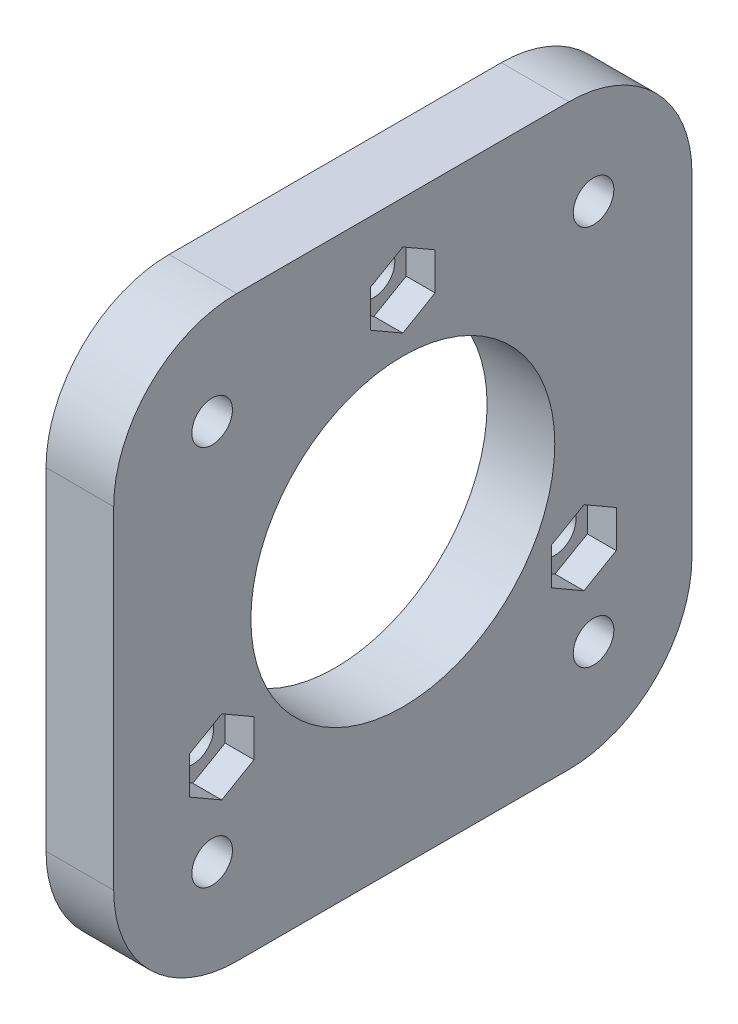
SolidWorks part; units mm, degrees
ref_plane "Alzado" through (0, 0, 0) normal (0, 0, 1) x (1, 0, 0)
ref_plane "Planta" through (0, 0, 0) normal (0, 1, 0) x (1, 0, 0)
ref_plane "Vista lateral" through (0, 0, 0) normal (1, 0, 0) x (0, 0, -1)
sketch "Croquis1" plane through (0, 0, 0) normal (1, 0, 0) x (0, 0, -1)
  line L0 (23.5, -23.5) -> (23.5, 23.5)
  line L1 (-15.5, -15.5) -> (15.5, -15.5) construction
  line L2 (-15.5, -15.5) -> (-15.5, 15.5) construction
  line L3 (-15.5, 15.5) -> (15.5, 15.5) construction
  line L4 (15.5, -15.5) -> (15.5, 15.5) construction
  line L5 (-15.5, -15.5) -> (15.5, 15.5) construction
  line L6 (-15.5, 15.5) -> (15.5, -15.5) construction
  line L7 (-23.5, 23.5) -> (23.5, 23.5)
  line L8 (-23.5, -23.5) -> (-23.5, 23.5)
  line L9 (-23.5, -23.5) -> (23.5, -23.5)
  circle A0 centre (-15.5, 15.5) radius 1.65
  circle A1 centre (15.5, 15.5) radius 1.65
  circle A2 centre (15.5, -15.5) radius 1.65
  circle A3 centre (-15.5, -15.5) radius 1.65
  point P0 (0, 0)
  point P16 (0, 0)
  dimension "D1" = 3.3
  dimension "D2" = 31
  dimension "D3" = 31
  dimension "D5" = 8
  dimension "D4" = 4
extrude "Saliente-Extruir1" add sketch "Croquis1" along normal blind 5.5
sketch "Croquis2" plane through (5.5, 0, 0) normal (1, 0, 0) x (0, 0, -1)
  line L1 (0, 13.9689) -> (2.625, 15.4845)
  line L2 (2.625, 15.4845) -> (2.625, 18.5155)
  line L3 (2.625, 18.5155) -> (0, 20.0311)
  line L4 (0, 20.0311) -> (-2.625, 18.5155)
  line L5 (-2.625, 18.5155) -> (-2.625, 15.4845)
  line L6 (-2.625, 15.4845) -> (0, 13.9689)
  line L24 (14.7224, -11.5311) -> (17.3474, -10.0155)
  line L25 (17.3474, -10.0155) -> (17.3474, -6.9845)
  line L26 (17.3474, -6.9845) -> (14.7224, -5.4689)
  line L27 (14.7224, -5.4689) -> (12.0974, -6.9845)
  line L28 (12.0974, -6.9845) -> (12.0974, -10.0155)
  line L29 (12.0974, -10.0155) -> (14.7224, -11.5311)
  line L30 (-17.3474, -6.9845) -> (-17.3474, -10.0155)
  line L31 (-17.3474, -10.0155) -> (-14.7224, -11.5311)
  line L32 (-14.7224, -11.5311) -> (-12.0974, -10.0155)
  line L33 (-12.0974, -10.0155) -> (-12.0974, -6.9845)
  line L34 (-12.0974, -6.9845) -> (-14.7224, -5.4689)
  line L35 (-14.7224, -5.4689) -> (-17.3474, -6.9845)
  circle A0 centre (0, 0) radius 17 construction
  circle A1 centre (0, 17) radius 2.625 construction
  point P26 (0, 0)
  dimension "D1" = 34
  dimension "D3" = 5.25
  dimension "D2" = 3
extrude "Cortar-Extruir1" cut sketch "Croquis2" against normal blind 2.35
sketch "Croquis7" plane through (5.5, 0, 0) normal (1, 0, 0) x (0, 0, -1)
  circle A0 centre (0, 0) radius 12.35
  dimension "D1" = 24.7
extrude "Cortar-Extruir2" cut sketch "Croquis7" against normal up to surface (5.5 mm away) up to face at (0, 0, 0)
sketch "Croquis8" plane through (5.5, 0, 0) normal (1, 0, 0) x (0, 0, -1)
  circle A0 centre (0, 17) radius 1.7
  circle A1 centre (14.7224, -8.5) radius 1.7
  circle A2 centre (-14.7224, -8.5) radius 1.7
  point P9 (0, 0)
  dimension "D1" = 3.4
  dimension "D2" = 3
extrude "Cortar-Extruir3" cut sketch "Croquis8" against normal up to surface (5.5 mm away) up to face at (0, 0, -12.35)
sketch "Croquis9" plane through (0, 0, 0) normal (-1, 0, 0) x (0, 0, 1)
  circle A0 centre (-15.5, -15.5) radius 3.25
  circle A1 centre (-15.5, 15.5) radius 3.25
  circle A2 centre (15.5, 15.5) radius 3.25
  circle A3 centre (15.5, -15.5) radius 3.25
  point P12 (0, 0)
  dimension "D1" = 6.5
  dimension "D2" = 4
extrude "Cortar-Extruir4" cut sketch "Croquis9" against normal blind 2.5
fillet "Redondeo1" radius 10 4 edges at (2.75, 23.5, 23.5) (2.75, 23.5, -23.5) (2.75, -23.5, -23.5) (2.75, -23.5, 23.5)
